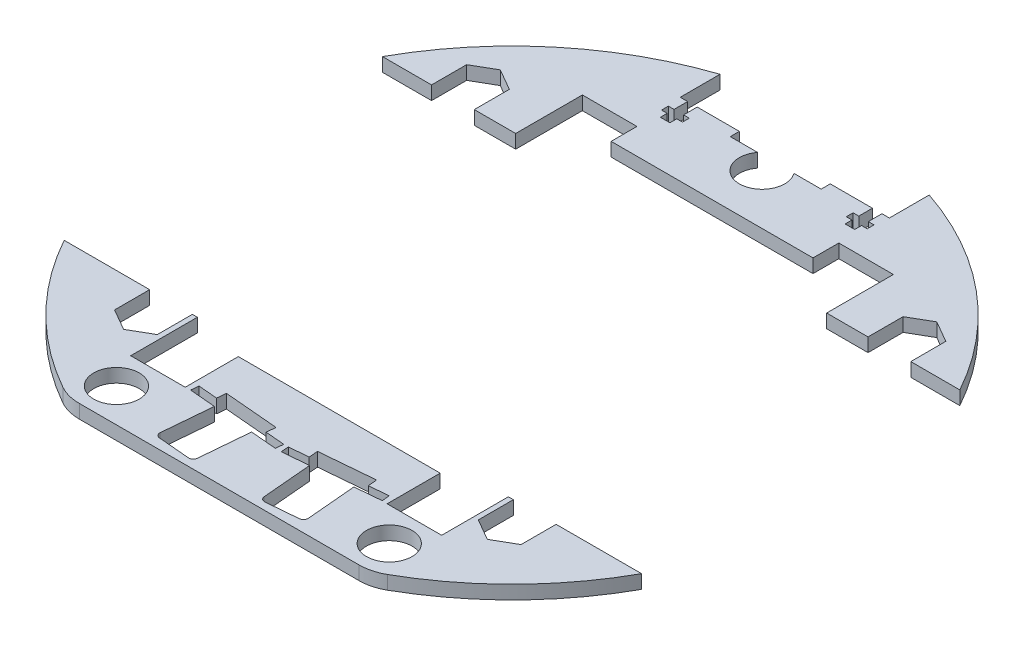
SolidWorks part; units mm, degrees
ref_plane "Front Plane" through (0, 0, 0) normal (0, 0, 1) x (1, 0, 0)
ref_plane "Top Plane" through (0, 0, 0) normal (0, 1, 0) x (1, 0, 0)
ref_plane "Right Plane" through (0, 0, 0) normal (1, 0, 0) x (0, 0, -1)
sketch "Sketch1" plane through (0, 0, 0) normal (0, 1, 0) x (1, 0, 0)
  line L0 (-30.7634, -64.4046) -> (30.7634, -64.4046)
  line L1 (0, -83.2398) -> (0, 0) construction
  line L2 (0, -83.2398) -> (33.2911, -64.4046) construction
  arc A0 (35.6856, -63.1093) -> (-35.6856, -63.1093) centre (0, 0) ccw
  circle A1 centre (0, -83.2398) radius 38.25 construction
  arc A2 (30.7634, -64.4046) -> (35.6856, -63.1093) centre (30.7634, -54.4046) ccw
  arc A3 (-30.7634, -64.4046) -> (-35.6856, -63.1093) centre (-30.7634, -54.4046) cw
  dimension "D1" = 145
  dimension "D2" = 76.5
  dimension "D4" = 10
  dimension "D3" = 60.5
extrude "Boss-Extrude1" add sketch "Sketch1" along normal blind 3
sketch "Sketch2" plane through (0, 3, 0) normal (0, 1, 0) x (1, 0, 0)
  line L29 (-22.2, -49.6757) -> (-22.2, -32.5) construction
  line L30 (-22.2, -49.6757) -> (-22.2, -32.5) construction
  line L38 (-34.2, -49.6757) -> (-22.2, -49.6757) construction
  line L39 (-34.2, -49.6757) -> (-34.2, 49.6757) construction
  line L40 (-34.2, 49.6757) -> (-22.2, 49.6757) construction
  line L41 (-22.2, 32.5) -> (-22.2, 49.6757) construction
  line L47 (22.2, 32.5) -> (22.2, 49.6757) construction
  line L48 (34.2, 49.6757) -> (22.2, 49.6757) construction
  line L49 (34.2, -49.6757) -> (34.2, 49.6757) construction
  line L50 (34.2, -49.6757) -> (22.2, -49.6757) construction
  line L51 (22.2, -49.6757) -> (22.2, -32.5) construction
  line L52 (22.2, -49.6757) -> (22.2, -32.5) construction
  line L53 (-22.2, -49.6757) -> (-22.2, -38) construction
  line L54 (-22.2, -49.6757) -> (-22.2, -38)
  line L55 (-22.2, 44) -> (22.2, 44)
  line L62 (-34.2, -49.6757) -> (-22.2, -49.6757)
  line L63 (-34.2, -49.6757) -> (-34.2, 49.6757)
  line L64 (-34.2, 49.6757) -> (-22.2, 49.6757)
  line L65 (-22.2, 44) -> (-22.2, 49.6757)
  line L71 (22.2, 44) -> (22.2, 49.6757)
  line L72 (34.2, 49.6757) -> (22.2, 49.6757)
  line L73 (34.2, -49.6757) -> (34.2, 49.6757)
  line L74 (34.2, -49.6757) -> (22.2, -49.6757)
  line L75 (22.2, -49.6757) -> (22.2, -38) construction
  line L76 (22.2, -49.6757) -> (22.2, -38)
  line L77 (-22.2, -38) -> (22.2, -38)
  dimension "D1" = 38
  dimension "D2" = 44
extrude "Cut-Extrude1" cut sketch "Sketch2" against normal through all contours L54 L77 L76 L74 L73 L72 L71 L55 L65 L64 L63 L62 region at (0, 3, -1.8128)
sketch "Sketch3" plane through (0, 3, 0) normal (0, 1, 0) x (1, 0, 0)
  line L0 (-34.2, 35) -> (-34.2, -35)
  line L1 (-72.5, -35) -> (-34.2, -35)
  line L2 (-72.5, -35) -> (-72.5, 35)
  line L3 (-72.5, 35) -> (-34.2, 35)
  line L4 (72.5, -35) -> (72.5, 35)
  line L5 (-72.5, -35) -> (72.5, 35) construction
  line L6 (-72.5, 35) -> (72.5, -35) construction
  line L8 (34.2, 35) -> (34.2, -35)
  line L10 (34.2, 35) -> (72.5, 35)
  line L11 (34.2, -35) -> (72.5, -35)
  line L12 (-34.2, -49.6757) -> (-34.2, 49.6757) construction
  line L13 (34.2, -49.6757) -> (34.2, 49.6757) construction
  arc A0 (35.6856, -63.1093) -> (-35.6856, -63.1093) centre (0, 0) ccw construction
  point P0 (0, 0)
  dimension "D1" = 70
extrude "Cut-Extrude2" cut sketch "Sketch3" against normal through all
sketch "Sketch4" plane through (0, 3, 0) normal (0, 1, 0) x (1, 0, 0)
  line L0 (-21.0702, -49.6179) -> (-0.6482, -51.4046)
  line L1 (21.0702, -49.6179) -> (20.922, -47.9244)
  line L2 (0.6482, -51.4046) -> (0.5, -49.7111)
  line L3 (20.922, -47.9244) -> (0.5, -49.7111)
  line L4 (0, 0) -> (0, -64.4046) construction
  line L5 (-30.7634, -64.4046) -> (30.7634, -64.4046) construction
  line L6 (-20.922, -47.9244) -> (-0.5, -49.7111)
  line L7 (-0.6482, -51.4046) -> (-0.5, -49.7111)
  line L8 (-21.0702, -49.6179) -> (-20.922, -47.9244)
  line L14 (21.0702, -49.6179) -> (0.6482, -51.4046)
  dimension "D1" = 1.7
  dimension "D2" = 20.5
  dimension "D3" = 5
  dimension "D4" = 13
  dimension "D5" = 0.5
extrude "Cut-Extrude3" cut sketch "Sketch4" against normal through all
sketch "Sketch5" plane through (0, 3, 0) normal (0, 1, 0) x (1, 0, 0)
  line L0 (6.3763, -50.9035) -> (15.342, -50.1191)
  line L1 (6.3763, -50.9035) -> (7.335, -61.8616)
  line L2 (15.342, -50.1191) -> (16.3007, -61.0772)
  line L3 (8.4183, -62.7706) -> (15.3917, -62.1605)
  line L4 (0.6482, -51.4046) -> (21.0702, -49.6179) construction
  line L5 (16.6882, -48.2948) -> (4.7338, -49.3407)
  line L6 (16.6882, -48.2948) -> (16.5139, -46.3024)
  line L7 (4.7338, -49.3407) -> (4.5595, -47.3483)
  line L8 (16.5139, -46.3024) -> (4.5595, -47.3483)
  line L9 (20.922, -47.9244) -> (0.5, -49.7111) construction
  line L10 (0, -38) -> (0, -64.4046) construction
  line L12 (-30.7634, -64.4046) -> (30.7634, -64.4046) construction
  line L13 (-16.5139, -46.3024) -> (-4.5595, -47.3483)
  line L14 (-4.7338, -49.3407) -> (-4.5595, -47.3483)
  line L15 (-16.6882, -48.2948) -> (-16.5139, -46.3024)
  line L16 (-16.6882, -48.2948) -> (-4.7338, -49.3407)
  line L17 (-8.4183, -62.7706) -> (-15.3917, -62.1605)
  line L18 (-15.342, -50.1191) -> (-16.3007, -61.0772)
  line L19 (-6.3763, -50.9035) -> (-7.335, -61.8616)
  line L20 (-6.3763, -50.9035) -> (-15.342, -50.1191)
  line L21 (-22.2, -38) -> (22.2, -38) construction
  arc A0 (16.3007, -61.0772) -> (15.3917, -62.1605) centre (15.3046, -61.1643) cw
  arc A1 (7.335, -61.8616) -> (8.4183, -62.7706) centre (8.3312, -61.7744) ccw
  arc A2 (-7.335, -61.8616) -> (-8.4183, -62.7706) centre (-8.3312, -61.7744) cw
  arc A3 (-16.3007, -61.0772) -> (-15.3917, -62.1605) centre (-15.3046, -61.1643) ccw
  point P14 (10.711, -48.8177)
  point P15 (10.711, -48.8177)
  point P17 (10.8592, -50.5113)
  point P18 (10.8592, -50.5113)
  point P21 (16.3879, -62.0734)
  point P24 (7.4222, -62.8578)
  point P40 (-7.4222, -62.8578)
  point P41 (-16.3879, -62.0734)
  dimension "D5" = 1
  dimension "D1" = 12
  dimension "D2" = 9
  dimension "D3" = 12
  dimension "D4" = 2
extrude "Cut-Extrude4" cut sketch "Sketch5" against normal through all
sketch "Sketch6" plane through (0, 3, 0) normal (0, 1, 0) x (1, 0, 0)
  line L0 (0, 0) -> (0, 60) construction
  line L1 (-23, 72.5) -> (23, 72.5)
  line L2 (-23, 72.5) -> (-23, 60)
  line L3 (-23, 60) -> (-10, 60)
  line L4 (23, 72.5) -> (23, 60)
  line L5 (10, 60) -> (23, 60)
  line L7 (10, 60) -> (10, 58)
  line L8 (10, 58) -> (-10, 58)
  line L9 (-10, 60) -> (-10, 58)
  arc A1 (63.4921, 35) -> (-63.4921, 35) centre (0, 0) ccw construction
  point P14 (0, 58)
  dimension "D1" = 20
  dimension "D2" = 46
  dimension "D3" = 60
  dimension "D4" = 2
extrude "Cut-Extrude5" cut sketch "Sketch6" against normal through all
sketch "Sketch7" plane through (0, 3, 0) normal (0, 1, 0) x (1, 0, 0)
  circle A1 centre (-30, -57) radius 5
  circle A2 centre (-30, -57) radius 5
  circle A3 centre (30, -57) radius 5
  circle A4 centre (30, -57) radius 5
  dimension "D1" = 0
  dimension "D2" = 0
extrude "Cut-Extrude6" cut sketch "Sketch7" against normal through all
sketch "Sketch8" plane through (0, 3, 0) normal (0, 1, 0) x (1, 0, 0)
  line L10 (-52.7, 37.2865) -> (-52.7, 32.5)
  line L11 (-52.7, 32.5) -> (-43.3, 32.5)
  line L12 (-43.3, 32.5) -> (-43.3, 37.2865)
  line L13 (-43.3, 37.2865) -> (-43.3, 42.7135)
  line L14 (-43.3, 42.7135) -> (-48, 45.4271)
  line L15 (-48, 45.4271) -> (-52.7, 42.7135)
  line L16 (-52.7, 42.7135) -> (-52.7, 37.2865)
  line L17 (-52.7, 37.2865) -> (-52.7, 32.5)
  line L18 (-52.7, 32.5) -> (-43.3, 32.5)
  line L19 (-43.3, 32.5) -> (-43.3, 37.2865)
  line L20 (-43.3, 37.2865) -> (-43.3, 42.7135)
  line L21 (-43.3, 42.7135) -> (-48, 45.4271)
  line L22 (-48, 45.4271) -> (-52.7, 42.7135)
  line L23 (-52.7, 42.7135) -> (-52.7, 37.2865)
  line L24 (44.7, -32.5) -> (35.3, -32.5)
  line L25 (44.7, -37.2865) -> (44.7, -32.5)
  line L26 (44.7, -42.7135) -> (44.7, -37.2865)
  line L31 (40, -45.4271) -> (44.7, -42.7135)
  line L32 (35.3, -42.7135) -> (40, -45.4271)
  line L33 (35.3, -37.2865) -> (35.3, -42.7135)
  line L34 (35.3, -32.5) -> (35.3, -37.2865)
  line L35 (44.7, -32.5) -> (35.3, -32.5)
  line L36 (44.7, -37.2865) -> (44.7, -32.5)
  line L37 (44.7, -42.7135) -> (44.7, -37.2865)
  line L38 (40, -45.4271) -> (44.7, -42.7135)
  line L39 (35.3, -42.7135) -> (40, -45.4271)
  line L40 (35.3, -37.2865) -> (35.3, -42.7135)
  line L41 (35.3, -32.5) -> (35.3, -37.2865)
  line L42 (-35.3, -37.2865) -> (-35.3, -32.5)
  line L43 (-35.3, -32.5) -> (-44.7, -32.5)
  line L44 (-44.7, -32.5) -> (-44.7, -37.2865)
  line L45 (-44.7, -37.2865) -> (-44.7, -42.7135)
  line L46 (-44.7, -42.7135) -> (-40, -45.4271)
  line L47 (-40, -45.4271) -> (-35.3, -42.7135)
  line L48 (-35.3, -42.7135) -> (-35.3, -37.2865)
  line L49 (-35.3, -37.2865) -> (-35.3, -32.5)
  line L50 (-35.3, -32.5) -> (-44.7, -32.5)
  line L51 (-44.7, -32.5) -> (-44.7, -37.2865)
  line L52 (-44.7, -37.2865) -> (-44.7, -42.7135)
  line L53 (-44.7, -42.7135) -> (-40, -45.4271)
  line L54 (-40, -45.4271) -> (-35.3, -42.7135)
  line L55 (-35.3, -42.7135) -> (-35.3, -37.2865)
  line L56 (52.7, 32.5) -> (52.7, 37.2865)
  line L57 (52.7, 37.2865) -> (52.7, 42.7135)
  line L58 (52.7, 42.7135) -> (48, 45.4271)
  line L59 (48, 45.4271) -> (43.3, 42.7135)
  line L60 (43.3, 42.7135) -> (43.3, 37.2865)
  line L61 (43.3, 37.2865) -> (43.3, 32.5)
  line L62 (43.3, 32.5) -> (52.7, 32.5)
  line L63 (52.7, 32.5) -> (52.7, 37.2865)
  line L64 (52.7, 37.2865) -> (52.7, 42.7135)
  line L65 (52.7, 42.7135) -> (48, 45.4271)
  line L66 (48, 45.4271) -> (43.3, 42.7135)
  line L67 (43.3, 42.7135) -> (43.3, 37.2865)
  line L68 (43.3, 37.2865) -> (43.3, 32.5)
  line L69 (43.3, 32.5) -> (52.7, 32.5)
  dimension "D1" = 0
  dimension "D2" = 0
  dimension "D3" = 0
  dimension "D4" = 0
extrude "Cut-Extrude7" cut sketch "Sketch8" against normal through all
sketch "Sketch9" plane through (0, 3, 0) normal (0, 1, 0) x (1, 0, 0)
  line L0 (-23, 60) -> (-10, 60) construction
  line L1 (22.62, 57) -> (18.02, 57)
  line L2 (22.62, 57) -> (22.62, 55.5)
  line L3 (22.62, 55.5) -> (18.02, 55.5)
  line L4 (18.02, 57) -> (18.02, 55.5)
  line L5 (0, 0) -> (0, 44) construction
  line L6 (-22.2, 44) -> (22.2, 44) construction
  line L7 (-18.02, 57) -> (-18.02, 55.5)
  line L8 (-22.62, 55.5) -> (-18.02, 55.5)
  line L9 (-22.62, 57) -> (-22.62, 55.5)
  line L10 (-22.62, 57) -> (-18.02, 57)
  point P4 (20.32, 55.5)
  dimension "D1" = 20.32
  dimension "D2" = 1.5
  dimension "D3" = 4.6
  dimension "D4" = 3
extrude "Cut-Extrude8" cut sketch "Sketch9" against normal through all
sketch "Sketch10" plane through (0, 3, 0) normal (0, 1, 0) x (1, 0, 0)
  line L0 (22.62, 57) -> (18.02, 57) construction
  line L1 (21.37, 57) -> (19.27, 57)
  line L2 (21.37, 57) -> (21.37, 60)
  line L3 (21.37, 60) -> (19.27, 60)
  line L4 (19.27, 57) -> (19.27, 60)
  line L5 (-23, 60) -> (-10, 60) construction
  line L6 (0, 0) -> (0, 44) construction
  line L7 (-22.2, 44) -> (22.2, 44) construction
  line L8 (18.02, 55.5) -> (22.62, 55.5) construction
  line L9 (21.37, 55.5) -> (19.27, 55.5)
  line L10 (21.37, 55.5) -> (21.37, 54)
  line L11 (21.37, 54) -> (19.27, 54)
  line L12 (19.27, 55.5) -> (19.27, 54)
  line L13 (-19.27, 55.5) -> (-19.27, 54)
  line L14 (-21.37, 54) -> (-19.27, 54)
  line L15 (-21.37, 55.5) -> (-21.37, 54)
  line L16 (-21.37, 55.5) -> (-19.27, 55.5)
  line L17 (-19.27, 57) -> (-19.27, 60)
  line L18 (-21.37, 60) -> (-19.27, 60)
  line L19 (-21.37, 57) -> (-21.37, 60)
  line L20 (-21.37, 57) -> (-19.27, 57)
  point P14 (20.32, 57)
  point P16 (20.32, 57)
  dimension "D1" = 2.1
  dimension "D2" = 6
extrude "Cut-Extrude9" cut sketch "Sketch10" against normal through all
sketch "Sketch11" plane through (0, 3, 0) normal (0, 1, 0) x (1, 0, 0)
  line L0 (0, 0) -> (0, 55) construction
  circle A0 centre (0, 55) radius 5
  dimension "D2" = 10
  dimension "D1" = 55
extrude "Cut-Extrude10" cut sketch "Sketch11" against normal through all
equation "\"smallPulleyTeeth\"= 30"
equation "\"largePulleyTeeth\"= 30"
equation "\"eighthThick\"= 3.0mm"
equation "\"sixteenthThick\"= 1.7mm"
equation "\"quarterThick\"=6.0mm"
equation "\"OD\"= 145mm"
equation "\"puckAngle\"= 60.5deg"
equation "\"puckDiam\"= 76.5mm"
equation "\"axlePress\"= 5.9mm"
equation "\"press\"= 0.2mm"
equation "\"wheelClear\"= 0.3mm"
equation "\"10-32clear\"= 4.8mm"
equation "\"6-32clear\"= 3.3mm"
equation "\"8-32clear\"= 4.0mm"
equation "\"4-40clear\"= 3.0mm"
equation "\"wheelHeight\"= 22mm"
equation "\"wheelWell\"= 65mm"
equation "\"D1@Sketch1\"=\"OD\""
equation "\"D1@Boss-Extrude1\"=\"eighthThick\""
equation "\"D2@Sketch1\"=\"puckDiam\""
equation "\"D3@Sketch1\"=\"puckAngle\""
